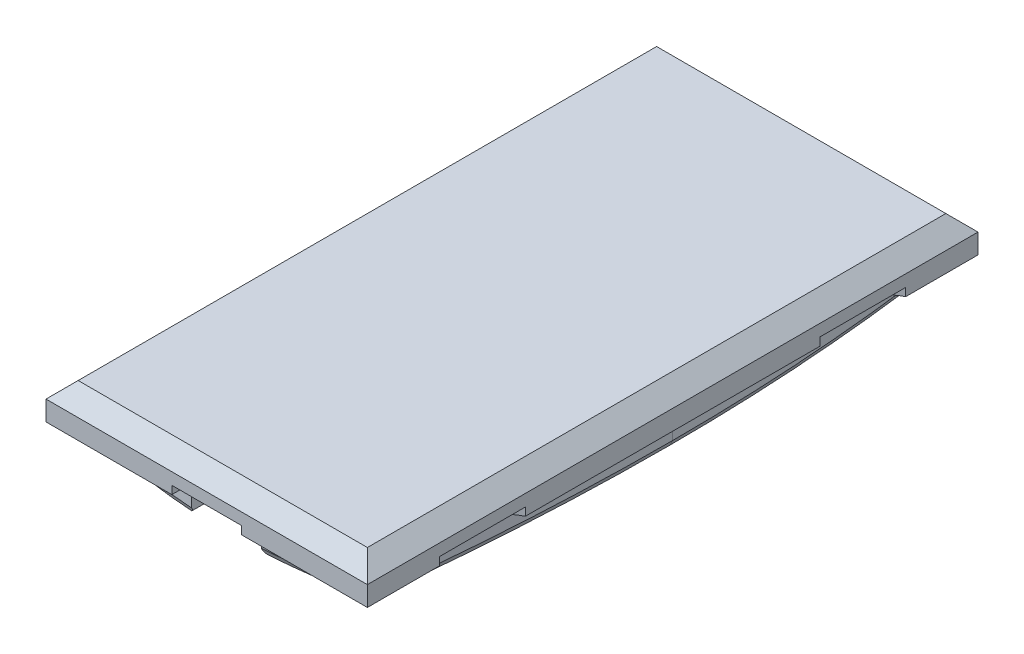
SolidWorks part; units mm, degrees
ref_plane "Front Plane" through (0, 0, 0) normal (0, 0, 1) x (1, 0, 0)
ref_plane "Top Plane" through (0, 0, 0) normal (0, 1, 0) x (1, 0, 0)
ref_plane "Right Plane" through (0, 0, 0) normal (1, 0, 0) x (0, 0, -1)
sketch "Sketch1" plane through (0, 0, 0) normal (0, 1, 0) x (1, 0, 0)
  line L1 (-40.4516, 33.2536) -> (19.5484, 33.2536)
  line L2 (-40.4516, 33.2536) -> (-40.4516, -80.7464)
  line L3 (-40.4516, -80.7464) -> (19.5484, -80.7464)
  line L4 (19.5484, 33.2536) -> (19.5484, -80.7464)
  dimension "D1" = 114
  dimension "D2" = 60
extrude "Boss-Extrude1" add sketch "Sketch1" along normal blind 11.7
chamfer "Chamfer1" distance 3 distance2 3 4 edges at (-10.4516, 11.7, -33.2536) (19.5484, 11.7, 23.7464) (-10.4516, 11.7, 80.7464) (-40.4516, 11.7, 23.7464)
sketch "Sketch2" plane through (0, 0, 0) normal (0, -1, 0) x (1, 0, 0)
  line L0 (-1161.9057, 32026.3942) -> (-1185.7752, 31888.444) construction
  line L1 (120.5746, -543.615) -> (97.9586, 205.7525) construction
  line L2 (-1226.5, 214.1667) -> (-1226.5, 1070.8333) construction
  line L3 (-19.0642, 122.1549) -> (-19.6382, -17.844) construction
  line L4 (-37.3001, 78.378) -> (-37.9372, -35.6202) construction
  line L5 (-40.1354, 80.6635) -> (-40.2952, -33.3364) construction
  line L6 (19.5484, 80.7464) -> (19.5484, -33.2536) construction
  line L7 (-16.9516, 66.7464) -> (-3.9516, 66.7464)
  line L8 (12.0484, 66.7464) -> (-32.9516, 66.7464)
  line L9 (19.5484, -33.2536) -> (-40.4516, -33.2536) construction
  line L11 (-10.4516, 66.7464) -> (-10.4516, -33.2536) construction
  line L12 (-16.9516, 66.7464) -> (-3.9516, 66.7464)
  line L13 (-32.9516, 66.7464) -> (12.0484, 66.7464)
  line L14 (-32.9516, 66.7464) -> (-32.9516, -33.2536)
  line L15 (-32.9516, -33.2536) -> (12.0484, -33.2536) construction
  line L16 (12.0484, 66.7464) -> (12.0484, -33.2536)
  line L17 (-16.9516, 66.7464) -> (-16.9516, 77.0538)
  line L18 (-20.9175, 76.7464) -> (0.0144, 76.7464)
  line L19 (-3.9516, 66.7464) -> (-3.9516, 77.0538)
  line L20 (-32.9516, -29.2536) -> (12.0484, -29.2536)
  line L21 (13.5484, 77.2464) -> (-34.4516, 77.2464) construction
  line L22 (17.0484, 77.2464) -> (-37.9516, 77.2464) construction
  line L23 (17.0484, 77.2464) -> (17.0484, -29.7536) construction
  line L24 (17.0484, -29.7536) -> (-37.9516, -29.7536) construction
  line L25 (-40.4516, 80.7464) -> (-40.4516, -33.2536)
  line L26 (-40.4516, -33.2536) -> (19.5484, -33.2536)
  line L27 (19.5484, -33.2536) -> (19.5484, 80.7464)
  line L28 (19.5484, 80.7464) -> (-40.4516, 80.7464)
  line L29 (-40.4516, 80.7464) -> (-40.4516, -33.2536)
  line L30 (-40.4516, -33.2536) -> (19.5484, -33.2536)
  line L31 (19.5484, -33.2536) -> (19.5484, 80.7464)
  line L32 (19.5484, 80.7464) -> (-40.4516, 80.7464)
  line L33 (-37.9516, 77.2464) -> (-37.9516, -29.7536) construction
  line L34 (17.0484, -26.2536) -> (17.0484, 73.7464) construction
  line L35 (13.5484, -29.7536) -> (-34.4516, -29.7536) construction
  line L36 (-37.9516, -26.2536) -> (-37.9516, 73.7464) construction
  line L38 (19.5484, 80.7464) -> (-40.4516, 80.7464)
  line L39 (19.5484, 80.7464) -> (19.5484, -33.2536)
  line L40 (19.5484, -33.2536) -> (-40.4516, -33.2536)
  line L41 (-40.4516, 80.7464) -> (-40.4516, -33.2536)
  arc A0 (17.0484, 21.2464) -> (13.9157, -27.0152) centre (-356.273, 21.2464) cw
  arc A1 (-37.9516, 23.7464) -> (-34.8016, -27.0192) centre (372.6913, 23.7464) ccw
  arc A2 (17.0484, 21.2464) -> (13.8826, 74.5156) centre (-432.7016, 21.2464) ccw
  arc A3 (-34.8016, 74.512) -> (-37.9516, 23.7464) centre (372.6913, 23.7464) ccw
  arc A4 (13.8826, 74.5156) -> (-3.9516, 77.0538) centre (-10.4516, -32.5393) ccw
  arc A5 (-16.9516, 77.0538) -> (-34.8016, 74.512) centre (-10.4516, -32.5393) ccw
  circle A6 centre (-30.4516, 57.7464) radius 5
  circle A7 centre (9.5484, 57.7464) radius 5
  circle A8 centre (9.5484, -11.2536) radius 5
  circle A9 centre (-30.4516, -11.2536) radius 5
  arc A10 (-10.4516, -29.7536) -> (0.0144, -29.2536) centre (-10.4516, 80.0321) ccw construction
  arc A11 (-10.4516, -29.7536) -> (-20.9175, -29.2536) centre (-10.4516, 80.0321) cw construction
  arc A12 (13.8826, 74.5156) -> (13.5484, 77.2464) centre (-432.7016, 21.2464) ccw construction
  arc A13 (17.0484, 73.7464) -> (13.8826, 74.5156) centre (-10.4516, -32.5393) ccw construction
  arc A14 (-34.4516, 77.2464) -> (-34.8016, 74.512) centre (372.6913, 23.7464) ccw construction
  arc A15 (-34.8016, 74.512) -> (-37.9516, 73.7464) centre (-10.4516, -32.5393) ccw construction
  arc A16 (-34.8016, -27.0192) -> (-37.9516, -26.2536) centre (-10.4516, 80.0321) cw construction
  arc A17 (-34.8016, -27.0192) -> (-34.4516, -29.7536) centre (372.6913, 23.7464) ccw construction
  arc A18 (13.9157, -27.0152) -> (13.5484, -29.7536) centre (-356.273, 21.2464) cw construction
  arc A19 (13.9157, -27.0152) -> (17.0484, -26.2536) centre (-10.4516, 80.0321) ccw construction
  arc A20 (-3.9516, 77.0538) -> (-10.4516, 77.2464) centre (-10.4516, -32.5393) ccw construction
  arc A21 (-10.4516, 77.2464) -> (-16.9516, 77.0538) centre (-10.4516, -32.5393) ccw construction
  arc A22 (-32.9516, -27.4232) -> (-34.8016, -27.0192) centre (-10.4516, 80.0321) cw
  arc A23 (-20.9175, -29.2536) -> (-32.9516, -27.4232) centre (-10.4516, 80.0321) cw construction
  arc A24 (12.0484, -27.4232) -> (13.9157, -27.0152) centre (-10.4516, 80.0321) ccw
  arc A25 (0.0144, -29.2536) -> (12.0484, -27.4232) centre (-10.4516, 80.0321) ccw construction
  point P10 (-40.4516, 80.7464)
  point P29 (-10.4516, 66.7464)
  point P39 (-10.4516, 77.2464)
  point P55 (-10.4516, -29.7536)
  point P61 (17.0484, 23.7464)
  point P62 (17.0484, 21.2464)
  point P63 (-37.9516, 23.7464)
  dimension "D12" = 48
  dimension "D14" = 48
  dimension "D15" = 100
  dimension "D16" = 100
  dimension "D18" = 10
  dimension "D19" = 10
  dimension "D1" = 140
  dimension "D2" = 140
  dimension "D3" = 114
  dimension "D4" = 114
  dimension "D5" = 7.5
  dimension "D6" = 100
  dimension "D7" = 45
  dimension "D8" = 13
  dimension "D9" = 10
  dimension "D10" = 55
  dimension "D11" = 107
  dimension "D13" = 56
  dimension "D17" = 4
  dimension "D20" = 40
  dimension "D21" = 20
  dimension "D22" = 9
  dimension "D23" = 69
  dimension "D24" = 60
  dimension "D26" = 114
  dimension "D27" = 3.5
  dimension "D28" = 2.5
  dimension "D25" = 0
extrude "Cut-Extrude1" cut sketch "Sketch2" against normal blind 5
sketch "Sketch3" plane through (0, 5, 0) normal (0, -1, 0) x (1, 0, 0)
  line L0 (19.5484, 80.7464) -> (-40.4516, 80.7464) construction
  line L1 (-16.9516, 80.7464) -> (-3.9516, 80.7464)
  line L2 (-16.9516, 80.7464) -> (-16.9516, 62.7464)
  line L3 (-16.9516, 62.7464) -> (-3.9516, 62.7464)
  line L4 (-3.9516, 80.7464) -> (-3.9516, 62.7464)
  line L5 (-16.9516, 66.7464) -> (-16.9516, 77.0538) construction
  line L6 (-3.9516, 66.7464) -> (-3.9516, 77.0538) construction
  dimension "D1" = 18
extrude "Cut-Extrude2" cut sketch "Sketch3" against normal blind 1.5 contours L2 L1 L4 L3
sketch "Sketch4" plane through (0, 5, 0) normal (0, -1, 0) x (1, 0, 0)
  line L0 (12.0484, 53.4163) -> (12.0484, -6.9235) construction
  line L1 (-32.9516, -29.2536) -> (12.0484, -29.2536)
  line L2 (-32.9516, -29.2536) -> (-32.9516, 31.7464)
  line L3 (-32.9516, 31.7464) -> (12.0484, 31.7464)
  line L4 (12.0484, -29.2536) -> (12.0484, 31.7464)
  line L5 (-32.9516, 53.4163) -> (-32.9516, -6.9235) construction
  line L6 (-16.9516, 80.7464) -> (-40.4516, 80.7464) construction
  line L7 (-40.4516, -33.2536) -> (19.5484, -33.2536) construction
  dimension "D1" = 49
  dimension "D2" = 4
extrude "Cut-Extrude3" cut sketch "Sketch4" against normal blind 3
sketch "Sketch5" plane through (0, 8, 0) normal (0, -1, 0) x (1, 0, 0)
  line L0 (12.0484, 31.7464) -> (-32.9516, 31.7464) construction
  line L1 (-29.4516, 10.7464) -> (8.5484, 10.7464)
  line L2 (-29.4516, 10.7464) -> (-29.4516, -29.2536)
  line L3 (-29.4516, -29.2536) -> (8.5484, -29.2536)
  line L4 (8.5484, 10.7464) -> (8.5484, -29.2536)
  line L5 (-32.9516, -29.2536) -> (12.0484, -29.2536) construction
  point P6 (-10.4516, 31.7464)
  point P7 (-10.4516, 10.7464)
  dimension "D1" = 38
  dimension "D2" = 40
extrude "Cut-Extrude4" cut sketch "Sketch5" against normal blind 3 contours L2 L1 L4 L3
fillet "Fillet1" radius 3.5 10 edges at (-32.9516, 6.5, -29.2536) (-32.9516, 6.5, 31.7464) (12.0484, 6.5, 31.7464) (12.0484, 6.5, -29.2536) (-29.4516, 9.5, 10.7464) (8.5484, 9.5, 10.7464) (-32.9516, 2.5, -27.4232) (-32.9516, 2.5, 66.7464) (12.0484, 2.5, 66.7464) (12.0484, 2.5, -27.4232)
fillet "Fillet2" radius 2.5 2 edges at (-16.9516, 5.75, 62.7464) (-3.9516, 5.75, 62.7464)
fillet "Fillet3" radius 2 4 edges at (13.9157, 2.5, -27.0152) (-34.8016, 2.5, -27.0192) (-34.8016, 2.5, 74.512) (13.8826, 2.5, 74.5156)
chamfer "Chamfer2" distance 1 distance2 0.5 11 edges at (-32.9396, 0, -27.4257) (-34.4655, 0, -26.7201) (-37.9516, 0, 23.7464) (-34.4655, 0, 74.2129) (-25.2217, 0, 76.2483) (4.3065, 0, 76.25) (13.5423, 0, 74.2144) (16.298, 0, 47.2162) (16.3094, 0, -2.2316) (13.5842, 0, -26.7184) (12.0494, 0, -27.423) first distance on face at (-32.9395, 2.5, -27.4252) first distance on face at (-34.3281, 2.5, -26.5946) first distance on face at (-36.463, 2.5, 23.7464) first distance on face at (-34.3281, 2.5, 74.0874) first distance on face at (-25.2005, 2.5, 76.0925) first distance on face at (4.2855, 2.5, 76.0946) first distance on face at (13.4036, 2.5, 74.0882) first distance on face at (15.9234, 2.5, 47.1946) first distance on face at (15.9407, 2.5, -2.2084) first distance on face at (13.4484, 2.5, -26.5937) first distance on face at (12.0493, 2.5, -27.4225)
chamfer "Chamfer3" distance 0.5 angle 45 18 edges at (11.9947, 0, -26.3647) (12.0484, 0, -20.6686) (14.5484, 0, -11.2536) (12.0484, 0, 23.2464) (14.5484, 0, 57.7464) (12.0484, 0, 62.6615) (11.0233, 0, 65.7213) (2.2984, 0, 66.7464) (-3.9516, 0, 71.6497) (-16.9516, 0, 71.6497) (-32.9516, 0, 62.6615) (-23.2016, 0, 66.7464) (-31.9265, 0, 65.7213) (-32.8978, 0, -26.3647) (-35.4516, 0, 57.7464) (-32.9516, 0, 23.2464) (-35.4516, 0, -11.2536) (-32.9516, 0, -20.6686)
sketch "Sketch6" plane through (0, 5, 0) normal (0, -1, 0) x (1, 0, 0)
  line L0 (-37.4516, 76.7464) -> (16.5484, 76.7464) construction
  line L1 (-37.4516, 76.7464) -> (-37.4516, -29.2536) construction
  line L2 (-40.4516, 80.7464) -> (-40.4516, -33.2536) construction
  line L3 (-16.9516, 80.7464) -> (-3.9516, 80.7464) construction
  circle A0 centre (-37.4516, -29.2536) radius 1.5
  circle A1 centre (16.5484, -29.2536) radius 1.5
  circle A2 centre (16.5484, 76.7464) radius 1.5
  circle A3 centre (-37.4516, 76.7464) radius 1.5
  point P10 (-40.4516, 23.7464)
  point P11 (-37.4516, 23.7464)
  point P12 (-10.4516, 76.7464)
  point P15 (-10.4516, 80.7464)
  dimension "D1" = 3
  dimension "D2" = 106
  dimension "D3" = 54
extrude "Cut-Extrude5" cut sketch "Sketch6" against normal blind 3.5 contours A3 | A2 | A1 | A0
sketch "Sketch7" plane through (0, 5, 0) normal (0, -1, 0) x (1, 0, 0)
  line L0 (19.5484, -33.2536) -> (19.5484, 80.7464) construction
  line L1 (-10.4516, 80.7464) -> (-10.4516, -49919.2536) construction
  line L2 (-16.9516, 80.7464) -> (-3.9516, 80.7464) construction
  line L3 (-40.4516, -33.2536) -> (19.5484, -33.2536) construction
  line L4 (-40.4516, 23.7464) -> (49959.5484, 23.7464) construction
  line L5 (-40.4516, 80.7464) -> (-40.4516, -33.2536) construction
  line L6 (19.5484, -19.7536) -> (19.5484, -3.7536)
  line L7 (19.5484, 51.2464) -> (19.5484, 67.2464)
  line L8 (-40.4516, -19.7536) -> (-40.4516, -3.7536)
  line L9 (-40.4516, 51.2464) -> (-40.4516, 67.2464)
  arc A0 (19.5484, 67.2464) -> (19.5484, 51.2464) centre (23.4484, 59.2464) ccw
  arc A1 (-40.4516, 67.2464) -> (-40.4516, 51.2464) centre (-44.3516, 59.2464) cw
  arc A2 (19.5484, -19.7536) -> (19.5484, -3.7536) centre (23.4484, -11.7536) cw
  arc A3 (-40.4516, -19.7536) -> (-40.4516, -3.7536) centre (-44.3516, -11.7536) ccw
  point P3 (14.5484, 59.2464)
  point P11 (-10.4516, 80.7464)
  point P14 (-10.4516, -33.2536)
  point P19 (-40.4516, 23.7464)
  point P20 (19.5484, 23.7464)
  dimension "D1" = 5
  dimension "D2" = 16
  dimension "D3" = 13.5
extrude "Cut-Extrude6" cut sketch "Sketch7" against normal blind 1.5
ref_point "Point1"
